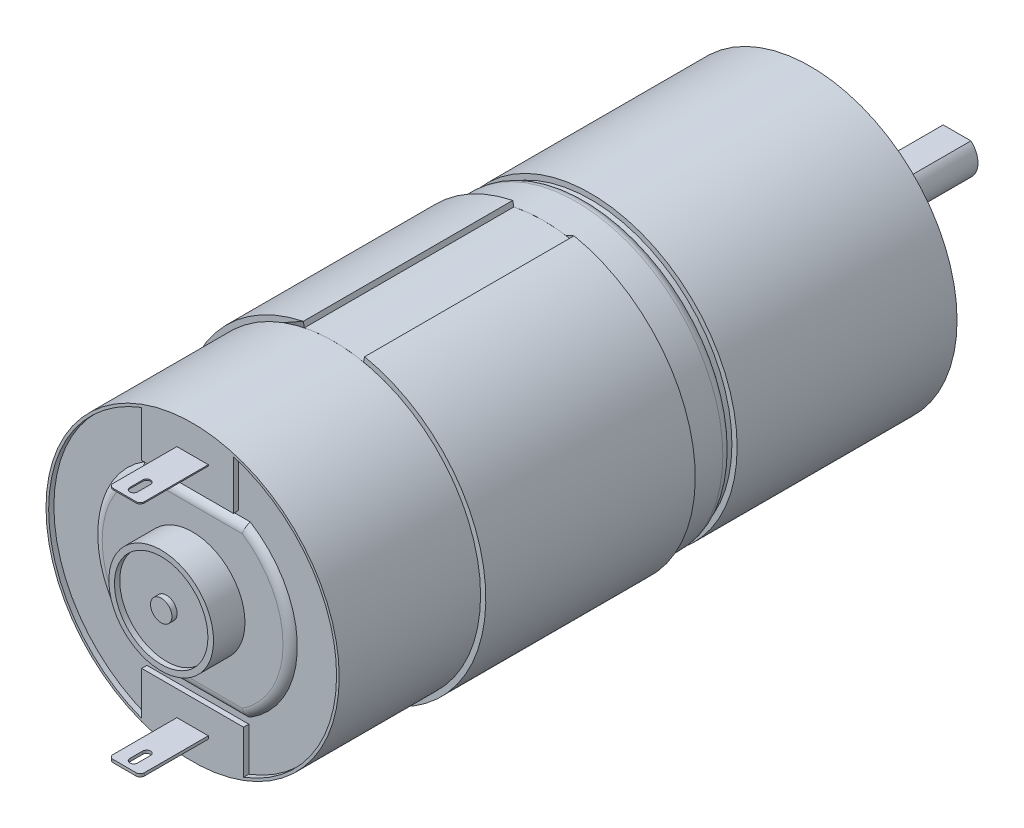
SolidWorks part; units mm, degrees
ref_plane "Front Plane" through (0, 0, 0) normal (0, 0, 1) x (1, 0, 0)
ref_plane "Top Plane" through (0, 0, 0) normal (0, 1, 0) x (1, 0, 0)
ref_plane "Right Plane" through (0, 0, 0) normal (1, 0, 0) x (0, 0, -1)
sketch "Sketch1" plane through (0, 0, 0) normal (0, 0, 1) x (1, 0, 0)
  circle A0 centre (0, 0) radius 14
  dimension "D1" = 28
extrude "Boss-Extrude1" add sketch "Sketch1" along normal blind 21
sketch "Sketch2" plane through (0, 0, 21) normal (0, 0, 1) x (1, 0, 0)
  circle A0 centre (0, 0) radius 13.5
extrude "Boss-Extrude2" add sketch "Sketch2" along normal blind 0.5
sketch "Sketch3" plane through (0, 0, 21.5) normal (0, 0, 1) x (1, 0, 0)
  circle A0 centre (0, 0) radius 14
extrude "Boss-Extrude3" add sketch "Sketch3" along normal blind 4
sketch "Sketch4" plane through (0, 0, 25.5) normal (0, 0, 1) x (1, 0, 0)
  circle A0 centre (0, 0) radius 14.5
extrude "Boss-Extrude4" add sketch "Sketch4" along normal blind 20
sketch "Sketch5" plane through (0, 0, 45.5) normal (0, 0, 1) x (1, 0, 0)
  circle A0 centre (0, 0) radius 14
extrude "Boss-Extrude5" add sketch "Sketch5" along normal blind 13
fillet "Fillet1" radius 1 1 edges at (14, 0, 21.5)
sketch "Sketch6" plane through (0, 0, 58.5) normal (0, 0, 1) x (1, 0, 0)
  line L1 (-5, -8.0777) -> (5, -8.0777)
  line L3 (-5, 8.0777) -> (5, 8.0777)
  line L5 (-5, -8.0777) -> (5, 8.0777) construction
  line L6 (-5, 8.0777) -> (5, -8.0777) construction
  arc A0 (-5, 8.0777) -> (-5, -8.0777) centre (0, 0) ccw
  arc A1 (5, -8.0777) -> (5, 8.0777) centre (0, 0) ccw
  circle A2 centre (0, 0) radius 14
  circle A3 centre (0, 0) radius 13.7479
  circle M2 centre (0, 0) radius 14
  dimension "D1" = 19
  dimension "D2" = 10
extrude "Boss-Extrude6" add sketch "Sketch6" along normal blind 0.5 contours L1 A1 L3 A0 | A3 M2 region at (0, 0, 58.5) region at (-13.9604, 0, 58.5)
fillet "Fillet2" radius 1 4 edges at (-9.5, 0, 59) (0, 8.0777, 59) (9.5, 0, 59) (0, -8.0777, 59)
sketch "Sketch7" plane through (0, 0, 59) normal (0, 0, 1) x (1, 0, 0)
  circle A0 centre (0, 0) radius 5
extrude "Boss-Extrude7" add sketch "Sketch7" along normal blind 3
sketch "Sketch8" plane through (0, 0, 62) normal (0, 0, 1) x (1, 0, 0)
  circle A0 centre (0, 0) radius 1.0212
  circle A1 centre (0, 0) radius 4.4608
extrude "Cut-Extrude1" cut sketch "Sketch8" against normal blind 0.5
sketch "Sketch9" plane through (0, 0, 58.5) normal (0, 0, 1) x (1, 0, 0)
  line L0 (-4.8645, 8.4747) -> (-4.8645, -8.7179) construction
  line L2 (-4.8645, 12.8585) -> (-4.8645, 8.4747)
  line L3 (-4.8645, 8.4747) -> (3.8986, 8.4747)
  line L4 (3.8986, 13.1836) -> (3.8986, 8.4747)
  line L5 (-0.4829, 13.7394) -> (3.8986, 8.4747) construction
  line L6 (-4.8645, 8.4747) -> (-0.4829, 13.7394) construction
  line L8 (-4.8645, -12.8585) -> (-4.8645, -8.7179)
  line L9 (-4.8645, -8.7179) -> (4.8645, -8.7179)
  line L10 (4.8645, -12.8585) -> (4.8645, -8.7179)
  line L11 (0, -13.7479) -> (4.8645, -8.7179) construction
  line L12 (-4.8645, -8.7179) -> (0, -13.7479) construction
  circle A0 centre (0, 0) radius 13.7479 construction
  circle A1 centre (0, 0) radius 13.7479 construction
  arc A2 (-4.8645, -12.8585) -> (4.8645, -12.8585) centre (0, 0) ccw
  arc A3 (3.8986, 13.1836) -> (-4.8645, 12.8585) centre (0, 0) ccw
  point P0 (-0.4829, 13.7394)
  point P9 (0, -13.7479)
extrude "Boss-Extrude8" add sketch "Sketch9" along normal blind 0.5
sketch "Sketch10" plane through (0, 0, 59) normal (0, 0, 1) x (1, 0, 0)
  line L0 (0, -11.25) -> (0, 11.25) construction
  line L1 (-1.5, 11.3065) -> (1.5, 11.3065)
  line L2 (-1.5, 11.3065) -> (-1.5, 11.1935)
  line L3 (-1.5, 11.1935) -> (1.5, 11.1935)
  line L4 (1.5, 11.3065) -> (1.5, 11.1935)
  line L5 (-1.5, 11.3065) -> (1.5, 11.1935) construction
  line L6 (-1.5, 11.1935) -> (1.5, 11.3065) construction
  line L7 (-1.5, -11.1112) -> (1.5, -11.1112)
  line L8 (-1.5, -11.1112) -> (-1.5, -11.3888)
  line L9 (-1.5, -11.3888) -> (1.5, -11.3888)
  line L10 (1.5, -11.1112) -> (1.5, -11.3888)
  line L11 (-1.5, -11.1112) -> (1.5, -11.3888) construction
  line L12 (-1.5, -11.3888) -> (1.5, -11.1112) construction
  line L13 (-1.5, 11.1935) -> (-1.5, -11.1112) construction
  point P0 (0, 11.25)
  point P5 (0, -11.25)
  point P12 (0, 0)
  dimension "D1" = 22.5
  dimension "D2" = 3
extrude "Boss-Extrude9" add sketch "Sketch10" along normal blind 6.5
fillet "Fillet3" radius 0.4 4 edges at (1.5, -11.25, 65.5) (-1.5, -11.25, 65.5) (-1.5, 11.25, 65.5) (1.5, 11.25, 65.5)
sketch "Sketch11" plane through (0, -11.3888, 0) normal (0, -1, 0) x (1, 0, 0)
  line L0 (0, 64.6227) -> (0, 63.389) construction
  line L1 (0.3725, 64.6227) -> (0.3725, 63.389)
  line L2 (-0.3725, 64.6227) -> (-0.3725, 63.389)
  arc A0 (0.3725, 64.6227) -> (-0.3725, 64.6227) centre (0, 64.6227) ccw
  arc A1 (-0.3725, 63.389) -> (0.3725, 63.389) centre (0, 63.389) ccw
  point P3 (0, 64.0058)
extrude "Cut-Extrude2" cut sketch "Sketch11" against normal through all
sketch "Sketch12" plane through (0, 0, 0) normal (0, 0, -1) x (-1, 0, 0)
  line L0 (2.6758, 7.2043) -> (3.8141, 10.269)
  line L1 (7.2043, 2.6758) -> (10.269, 3.8141)
  line L2 (4.1781, 11.2492) -> (11.2492, 4.1781) construction
  line L3 (0, 0) -> (7.7136, 7.7136) construction
  line L4 (0, 0) -> (12, 0) construction
  arc A0 (5.9715, 3.147) -> (3.147, 5.9715) centre (0, 0) ccw
  arc A1 (10.8228, 5.1834) -> (5.1834, 10.8228) centre (0, 0) ccw
  arc A2 (3.8141, 10.269) -> (5.1834, 10.8228) centre (4.7515, 9.9209) cw
  arc A3 (3.147, 5.9715) -> (2.6758, 7.2043) centre (3.6132, 6.8562) cw
  arc A4 (10.269, 3.8141) -> (10.8228, 5.1834) centre (9.9209, 4.7515) ccw
  arc A5 (7.2043, 2.6758) -> (5.9715, 3.147) centre (6.8562, 3.6132) cw
  dimension "D1" = 13.5
  dimension "D2" = 24
  dimension "D5" = 1
  dimension "D3" = 10
  dimension "D4" = 45
extrude "Cut-Extrude3" cut sketch "Sketch12" against normal blind 0.1 contours L1 A1 L0 A0 region at (-6.5999, 6.5999, 0)
pattern_circular "CirPattern1" count 4 every 90 about axis through (0, 0, 0) along (0, 0, 1) of "Cut-Extrude3"
sketch "Sketch13" plane through (0, 0, 25.5) normal (0, 0, -1) x (-1, 0, 0)
  line L0 (-2.8249, 13.7123) -> (-3, 14.5363)
  line L1 (2.8249, 13.7123) -> (3, 14.5363)
  line L2 (-3, 14.5363) -> (3, 14.5363) construction
  arc A0 (2.8249, 13.7123) -> (-2.8249, 13.7123) centre (0, 0) ccw
  arc A1 (3, 14.5363) -> (-3, 14.5363) centre (0, 0) ccw
  dimension "D1" = 6
extrude "Cut-Extrude4" cut sketch "Sketch13" against normal through all
sketch "Sketch15" plane through (0, 0, 0) normal (0, 0, -1) x (-1, 0, 0)
  circle A0 centre (0, 0) radius 3.5
extrude "Boss-Extrude10" add sketch "Sketch15" along normal blind 2
sketch "Sketch16" plane through (0, 0, -2) normal (0, 0, -1) x (-1, 0, 0)
  circle A0 centre (0, 0) radius 2
extrude "Boss-Extrude11" add sketch "Sketch16" along normal blind 12
sketch "Sketch17" plane through (0, 0, -14) normal (0, 0, -1) x (-1, 0, 0)
  line L0 (-1.3229, 1.5) -> (1.3229, 1.5)
  arc A0 (1.3229, 1.5) -> (-1.3229, 1.5) centre (0, 0) ccw
  circle A1 centre (0, 0) radius 2 construction
  dimension "D1" = 1.5
extrude "Cut-Extrude7" cut sketch "Sketch17" against normal blind 10
sketch "Sketch18" plane through (0, 0, 0) normal (0, 0, -1) x (-1, 0, 0)
  line L0 (-10, 0) -> (10, 0) construction
  circle A0 centre (-10, 0) radius 1.5
  circle A1 centre (10, 0) radius 1.5
  point P2 (0, 0)
  dimension "D2" = 3
  dimension "D3" = 3
  dimension "D1" = 20
extrude "Cut-Extrude8" cut sketch "Sketch18" against normal blind 10
